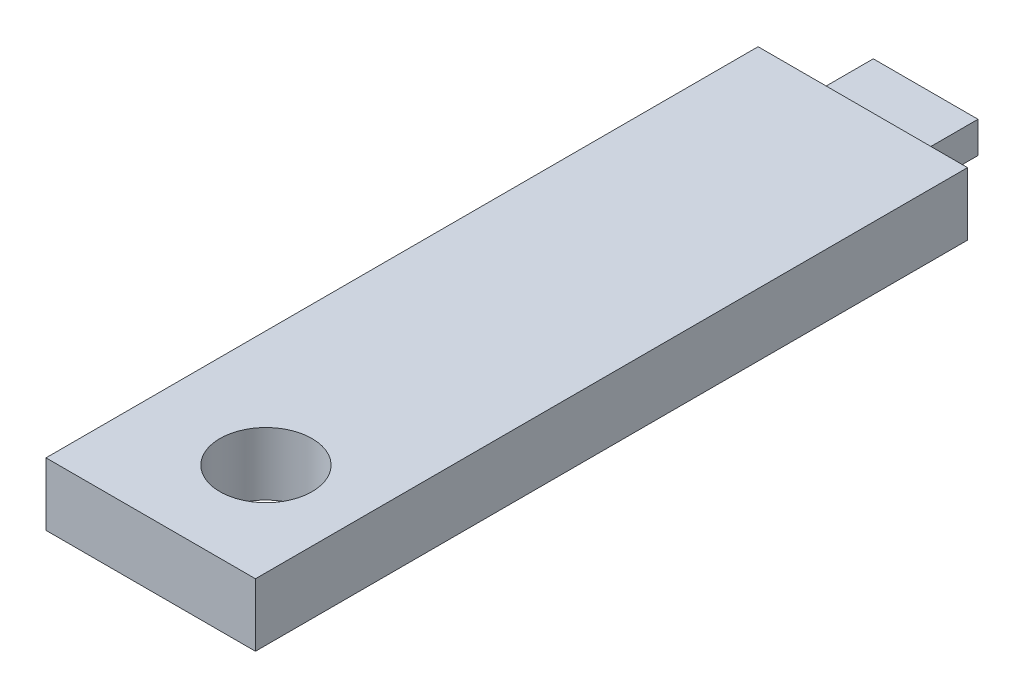
SolidWorks part; units mm, degrees
ref_plane "Front Plane" through (0, 0, 0) normal (0, 0, 1) x (1, 0, 0)
ref_plane "Top Plane" through (0, 0, 0) normal (0, 1, 0) x (1, 0, 0)
ref_plane "Right Plane" through (0, 0, 0) normal (1, 0, 0) x (0, 0, -1)
sketch "Sketch1" plane through (0, 0, 0) normal (0, 0, 1) x (1, 0, 0)
  line L1 (0, 0) -> (5, 0)
  line L2 (0, 0) -> (0, 1.5)
  line L3 (0, 1.5) -> (5, 1.5)
  line L4 (5, 0) -> (5, 1.5)
  dimension "D1" = 5
  dimension "D2" = 1.5
extrude "Boss-Extrude1" add sketch "Sketch1" along normal blind 3
sketch "Sketch2" plane through (0, 0, 3) normal (0, 0, 1) x (1, 0, 0)
  line L0 (0, 0) -> (5, 0) construction
  line L1 (-2.5, -0.75) -> (7.5, -0.75)
  line L2 (-2.5, -0.75) -> (-2.5, 2.25)
  line L3 (-2.5, 2.25) -> (7.5, 2.25)
  line L4 (7.5, -0.75) -> (7.5, 2.25)
  line L5 (0, 1.5) -> (0, 0) construction
  dimension "D1" = 10
  dimension "D2" = 3
  dimension "D3" = 0.75
  dimension "D4" = 2.5
extrude "Boss-Extrude2" add sketch "Sketch2" along normal blind 34
sketch "Sketch3" plane through (0, -0.75, 0) normal (0, -1, 0) x (1, 0, 0)
  circle A0 centre (3.0521, 32.0499) radius 2.2
  dimension "D1" = 4.4
extrude "Cut-Extrude1" cut sketch "Sketch3" against normal through all
